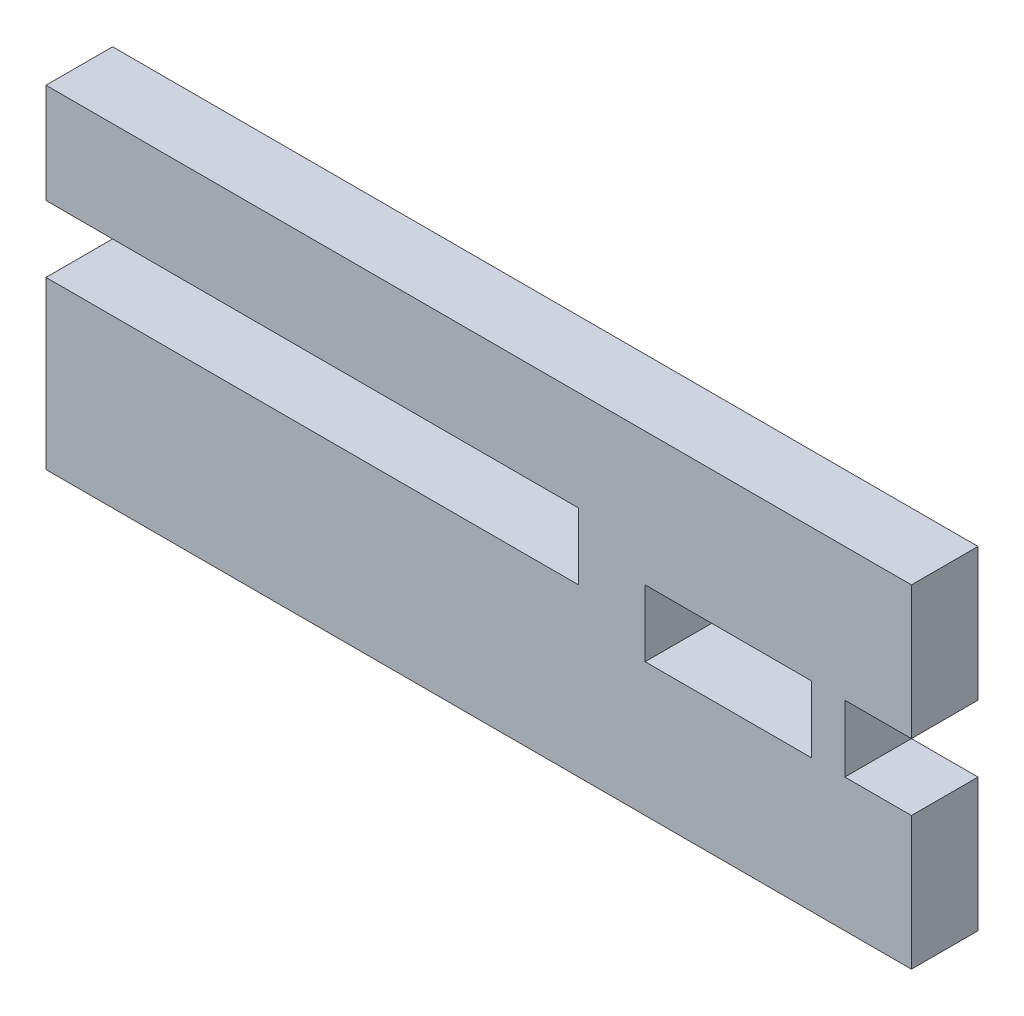
SolidWorks part; units mm, degrees
ref_plane "Front Plane" through (0, 0, 0) normal (0, 0, 1) x (1, 0, 0)
ref_plane "Top Plane" through (0, 0, 0) normal (0, 1, 0) x (1, 0, 0)
ref_plane "Right Plane" through (0, 0, 0) normal (1, 0, 0) x (0, 0, -1)
sketch "Sketch1" plane through (0, 0, 0) normal (0, 0, 1) x (1, 0, 0)
  line L1 (0, 0) -> (25.4, 0)
  line L2 (0, 0) -> (0, 4.7625)
  line L3 (0, 15.875) -> (25.4, 15.875)
  line L5 (0, 11.1125) -> (25.4, 11.1125)
  line L6 (0, 11.1125) -> (0, 4.7625) construction
  line L7 (0, 4.7625) -> (25.4, 4.7625)
  line L8 (25.4, 11.1125) -> (25.4, 4.7625)
  line L9 (25.4, 15.875) -> (41.275, 15.875)
  line L10 (25.4, 11.1125) -> (25.4, 4.7625)
  line L11 (25.4, 0) -> (41.275, 0)
  line L12 (0, 4.7625) -> (0, 11.1125) construction
  line L13 (0, 11.1125) -> (0, 15.875)
  line L14 (25.4, 11.1125) -> (25.4, 4.7625)
  line L15 (0, 4.7625) -> (25.4, 4.7625)
  line L16 (0, 4.7625) -> (0, 7.9375)
  line L17 (0, 7.9375) -> (25.4, 7.9375)
  line L18 (25.4, 4.7625) -> (25.4, 7.9375)
  line L19 (41.275, 15.875) -> (41.275, 0)
  line L20 (28.575, 9.525) -> (36.5125, 9.525)
  line L21 (28.575, 9.525) -> (28.575, 6.35)
  line L22 (28.575, 6.35) -> (36.5125, 6.35)
  line L23 (36.5125, 9.525) -> (36.5125, 6.35)
  line L24 (38.1, 9.525) -> (41.275, 9.525)
  line L25 (38.1, 9.525) -> (38.1, 6.35)
  line L26 (38.1, 6.35) -> (41.275, 6.35)
  line L27 (41.275, 9.525) -> (41.275, 6.35)
  point P21 (38.1, 7.9375)
  dimension "D5" = 7.9375
  dimension "D6" = 3.175
  dimension "D1" = 15.875
  dimension "D2" = 6.35
  dimension "D3" = 25.4
  dimension "D4" = 15.875
  dimension "D7" = 1.5875
  dimension "D8" = 3.175
  dimension "D9" = 7.9375
extrude "Boss-Extrude1" add sketch "Sketch1" along normal blind 3.175 contours L1 L3 L13 L5 L8 L7 L2 | L17 L16 L7 L8 region at (0.4422, 2.3812, 0) region at (12.7, 6.35, 0)
